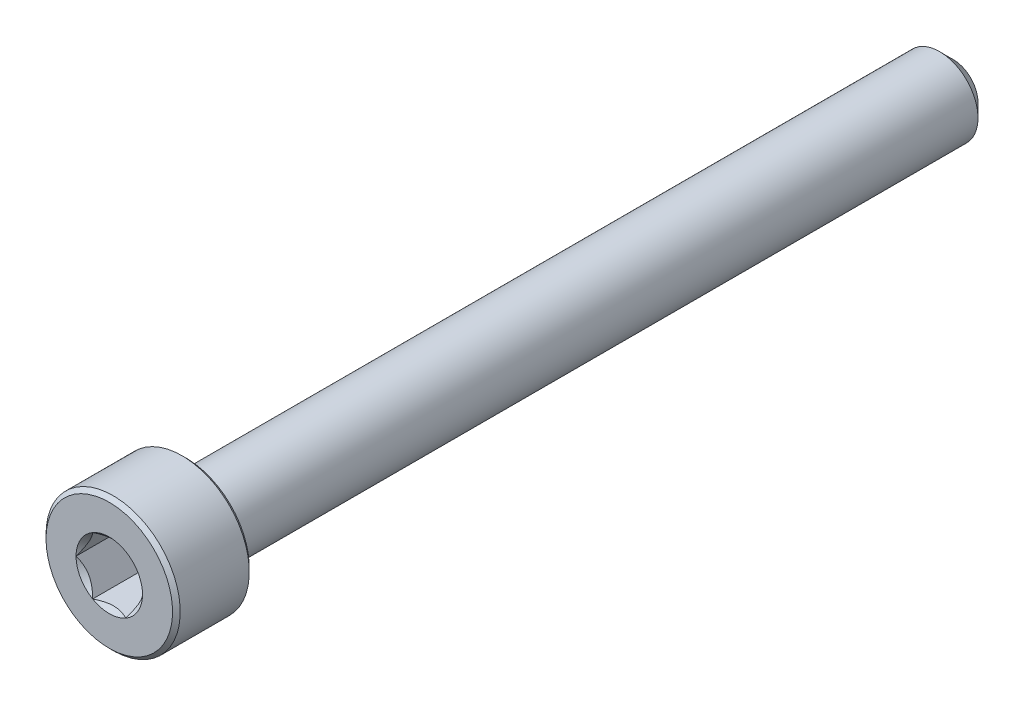
SolidWorks part; units mm, degrees
material "Alloy Steel"
ref_plane "Front Plane" through (0, 0, 0) normal (0, 0, 1) x (1, 0, 0)
ref_plane "Top Plane" through (0, 0, 0) normal (0, 1, 0) x (1, 0, 0)
ref_plane "Right Plane" through (0, 0, 0) normal (1, 0, 0) x (0, 0, -1)
sketch "Sketch1" plane through (0, 0, 0) normal (1, 0, 0) x (0, 0, -1)
  line L0 (-22, 0) -> (22, 0) construction
  line L1 (22, 0) -> (22, 1.3) construction
  line L2 (22, 1.3) -> (21.3, 2) construction
  line L3 (21.3, 2) -> (19.55, 2) construction
  line L4 (19.55, 2) -> (-18, 2) construction
  line L5 (-18, 2) -> (-18, 3.5) construction
  line L6 (-18, 3.5) -> (-22, 3.5) construction
  line L7 (-22, 3.5) -> (-22, 0) construction
  line L8 (22, 1.3) -> (22, 2) construction
  line L9 (21.9562, 2.0758) -> (22.3062, 1.4696) construction
  line L10 (22.3062, 1.4696) -> (22.6562, 2.0758) construction
  line L11 (22.6562, 2.0758) -> (21.9562, 2.0758) construction
  line L12 (22.3062, 2.0758) -> (22.3062, 2) construction
  line L13 (22.3062, 1.4696) -> (22.3062, 1.5453) construction
  line L14 (22.2625, 1.5453) -> (22.35, 1.5453) construction
  line L15 (22, 2) -> (22.6125, 2) construction
  line L16 (21.9781, 2.0379) -> (22.6344, 2.0379) construction
  line L17 (22, 0) -> (22, -2) construction
  line L18 (-18.2, 3.5) -> (-18, 3.3) construction
  line L19 (-21.8, 3.5) -> (-22, 3.3) construction
  point P0 (-22, 1.5)
  point P3 (19.55, 2)
  point P4 (0, 0)
  point P18 (18.55, 2)
  point P22 (22.3062, 1.5453)
  point P24 (19.55, 2)
  point P25 (22.3062, 2)
  point P28 (22.3062, 2.0379)
  point P29 (19.55, -2)
  point P30 (-17, 2)
  point P31 (-20, 3.5)
  point P37 (-18.7, 3.5)
  point P38 (-21.7, 3.5)
  dimension "head height" = 4
  dimension "D1" = 45
  dimension "head dia" = 7
  dimension "thread dia" = 4
  dimension "drive size" = 3
  dimension "pitch" = 0.7
  dimension "D2" = 0.0875
  dimension "D3" = 0.7
  dimension "D4" = 2.45
  dimension "D5" = 1
  dimension "D6" = 1
  dimension "D7" = 0.2
  dimension "D8" = 0.2
  dimension "D9" = 0.2
  dimension "D10" = 0.1
  dimension "D11" = 0.5
  dimension "length" = 40
sketch "Sketch2" plane through (0, 0, 0) normal (1, 0, 0) x (0, 0, -1)
  line L0 (-22, 0) -> (-22, 3.3)
  line L1 (-21.8, 3.5) -> (-18.2, 3.5)
  line L2 (-18, 3.3) -> (-18, 2)
  line L3 (-18, 2) -> (21.3, 2)
  line L4 (21.3, 2) -> (22, 1.3)
  line L5 (22, 1.3) -> (22, 0)
  line L6 (-18.2, 3.5) -> (-18, 3.3) construction
  line L7 (22, 0) -> (-22, 0)
  line L8 (-21.8, 3.5) -> (-22, 3.3) construction
  line L9 (-18.2, 3.5) -> (-18, 3.3)
  line L10 (-21.8, 3.5) -> (-22, 3.3)
revolve "Revolve1" add sketch "Sketch2" angle 360 about L7
sketch "Sketch3" plane through (0, 0, 22) normal (0, 0, 1) x (1, 0, 0)
  line L1 (0.866, 1.5) -> (-0.866, 1.5)
  line L2 (-0.866, 1.5) -> (-1.7321, 0)
  line L3 (-1.7321, 0) -> (-0.866, -1.5)
  line L4 (-0.866, -1.5) -> (0.866, -1.5)
  line L5 (0.866, -1.5) -> (1.7321, 0)
  line L6 (1.7321, 0) -> (0.866, 1.5)
  circle A0 centre (0, 0) radius 1.5 construction
extrude "Cut-Extrude1" cut sketch "Sketch3" against normal offset from surface (3 mm away) 1 up to face at (-3.3, 0, 18)
sketch "Sketch4" plane through (0, 0, 22) normal (0, 0, 1) x (1, 0, 0)
  circle A0 centre (0, 0) radius 1.7321
extrude "Cut-Extrude2" cut sketch "Sketch4" against normal up to vertex (2 mm away) draft 45 up to point (0, 3.5, 20)
ref_plane "Plane1" [suppressed] through (0, 0, -19.55) normal (0, 0, 1) x (1, 0, 0)
split "Split1" [suppressed] bodies to split 106
sketch "Sketch6" [suppressed] plane through (0, 0, -22) normal (0, 0, -1) x (-1, 0, 0)
  circle A0 centre (0, 0) radius 2
curve "Helix/Spiral1" [suppressed] pitch 0.7 height 40.7 turns 58.1429
sketch "Sketch7" [suppressed] plane through (0, 0, 0) normal (1, 0, 0) x (0, 0, -1)
  line L0 (21.9781, 2.0379) -> (22.6344, 2.0379)
  line L1 (22.6344, 2.0379) -> (22.35, 1.5453)
  line L2 (22.35, 1.5453) -> (22.2625, 1.5453)
  line L3 (22.2625, 1.5453) -> (21.9781, 2.0379)
sweep "Cut-Sweep1" [suppressed] cut profiles "Sketch7" path "Helix/Spiral1"
sketch "Sketch8" [suppressed] plane through (0, 0, 18) normal (0, 0, -1) x (-1, 0, 0)
  circle A0 centre (0, 0) radius 2
extrude "Boss-Extrude1" [suppressed] add sketch "Sketch8" along normal through all draft 70.5
equation "\"D2@Sketch1\"=\"pitch@Sketch1\"/8"
equation "\"D3@Sketch1\"=\"pitch@Sketch1\""
equation "\"D3@Helix/Spiral1\"=\"length@Sketch1\"+\"pitch@Sketch1\""
equation "\"D4@Helix/Spiral1\"=\"pitch@Sketch1\""
equation "\"D4@Sketch1\"=\"pitch@Sketch1\"*3.5"
equation "\"D7@Sketch1\"=\"head height@Sketch1\"*.05"
equation "\"D8@Sketch1\"=\"D7@Sketch1\""
equation "\"D9@Sketch1\"=\"D7@Sketch1\""
equation "\"D10@Sketch1\"=\"D7@Sketch1\"/2"
equation "\"D11@Sketch1\"=\"D10@Sketch1\"*5"
